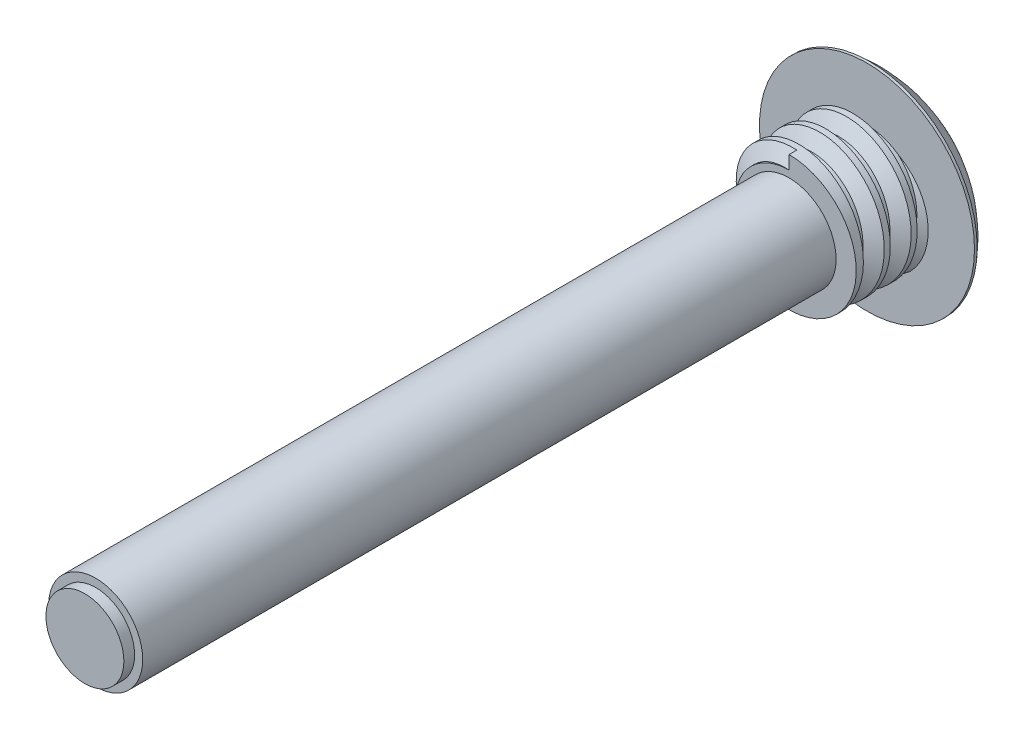
SolidWorks part; units mm, degrees
ref_plane "Front Plane" through (0, 0, 0) normal (0, 0, 1) x (1, 0, 0)
ref_plane "Top Plane" through (0, 0, 0) normal (0, 1, 0) x (1, 0, 0)
ref_plane "Right Plane" through (0, 0, 0) normal (1, 0, 0) x (0, 0, -1)
sketch "Sketch2" plane through (0, 0, 0) normal (0, 0, 1) x (1, 0, 0)
  circle A0 centre (0, 0) radius 3.175
curve "Helix/Spiral1" pitch 1.27 height 3.81 radius 3.175 left hand yes centre (0, 0, 0) axis (0, 0, 1) start towards (0, 1, 0)
sketch "Sketch3" plane through (0, 0, 0) normal (0, 0, 1) x (1, 0, 0)
  circle A0 centre (0, 0) radius 3.175
extrude "Boss-Extrude1" add sketch "Sketch3" along normal blind 3.683 contours A0
sketch "Sketch5" plane through (0, 0, 0) normal (1, 0, 0) x (0, 0, -1)
  line L0 (0.127, 2.54) -> (0.4936, 3.175)
  line L1 (0.4936, 3.175) -> (-0.4936, 3.175)
  line L2 (-0.4936, 3.175) -> (-0.127, 2.54)
  line L3 (-0.127, 2.54) -> (0.127, 2.54)
  line L4 (0, 3.175) -> (0, 2.54) construction
  dimension "D1" = 0.635
  dimension "D2" = 0.254
  dimension "D3" = 60
sweep "Cut-Sweep1" cut profiles "Sketch5" path "Helix/Spiral1" align with end faces yes
sketch "Sketch10" plane through (0, 0, 3.683) normal (0, 0, 1) x (1, 0, 0)
  circle A0 centre (0, 0) radius 2.2225
  dimension "D1" = 4.445
extrude "Boss-Extrude5" add sketch "Sketch10" along normal blind 32.766
sketch "Sketch9" plane through (0, 0, 0) normal (0, 0, 1) x (1, 0, 0)
  circle A0 centre (0, 0) radius 5.08
  dimension "D1" = 10.16
extrude "Boss-Extrude4" add sketch "Sketch9" against normal blind 0.127
dome "Dome3" faces to dome 1 distance 2.38 reverse direction no elliptical dome no face at (5.08, 0, -0.127) parameters "D1"=2.38
sketch "Sketch11" plane through (0, 0, 36.449) normal (0, 0, 1) x (1, 0, 0)
  circle A0 centre (0, 0) radius 1.8415
  dimension "D1" = 3.683
extrude "Boss-Extrude6" add sketch "Sketch11" along normal blind 0.508
